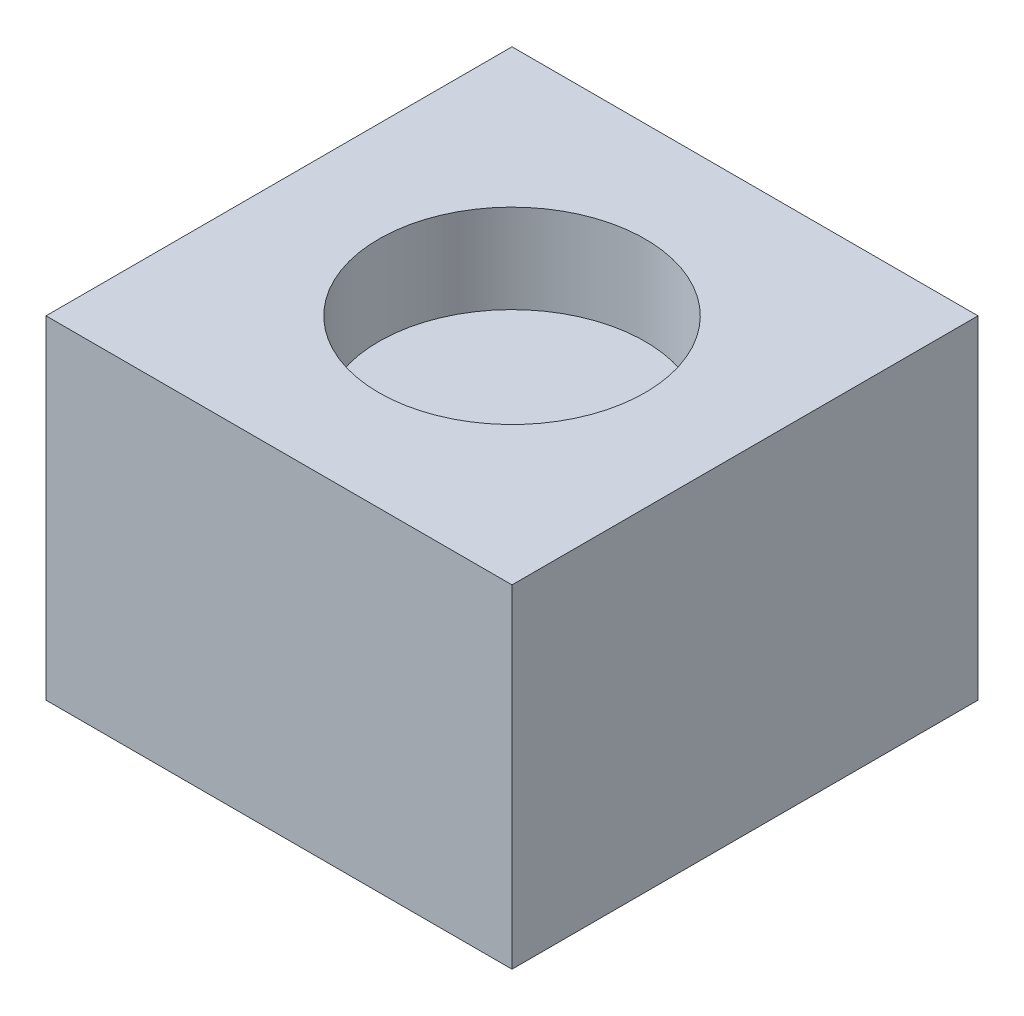
SolidWorks part; units mm, degrees
ref_plane "Plan de face" through (0, 0, 0) normal (0, 0, 1) x (1, 0, 0)
ref_plane "Plan de dessus" through (0, 0, 0) normal (0, 1, 0) x (1, 0, 0)
ref_plane "Plan de droite" through (0, 0, 0) normal (1, 0, 0) x (0, 0, -1)
sketch "Esquisse1" plane through (0, 0, 0) normal (0, 1, 0) x (1, 0, 0)
  line L1 (-21, 21) -> (21, 21)
  line L2 (-21, 21) -> (-21, -21)
  line L3 (-21, -21) -> (21, -21)
  line L4 (21, 21) -> (21, -21)
  line L5 (-21, 21) -> (21, -21) construction
  line L6 (-21, -21) -> (21, 21) construction
  point P0 (0, 0)
  dimension "D1" = 42
  dimension "D2" = 42
extrude "Boss.-Extru.1" add sketch "Esquisse1" along normal blind 30
sketch "Esquisse2" plane through (0, 30, 0) normal (0, 1, 0) x (1, 0, 0)
  circle A0 centre (0, 0) radius 12
  dimension "D1" = 24
extrude "Enlèv. mat.-Extru.1" cut sketch "Esquisse2" against normal blind 8
